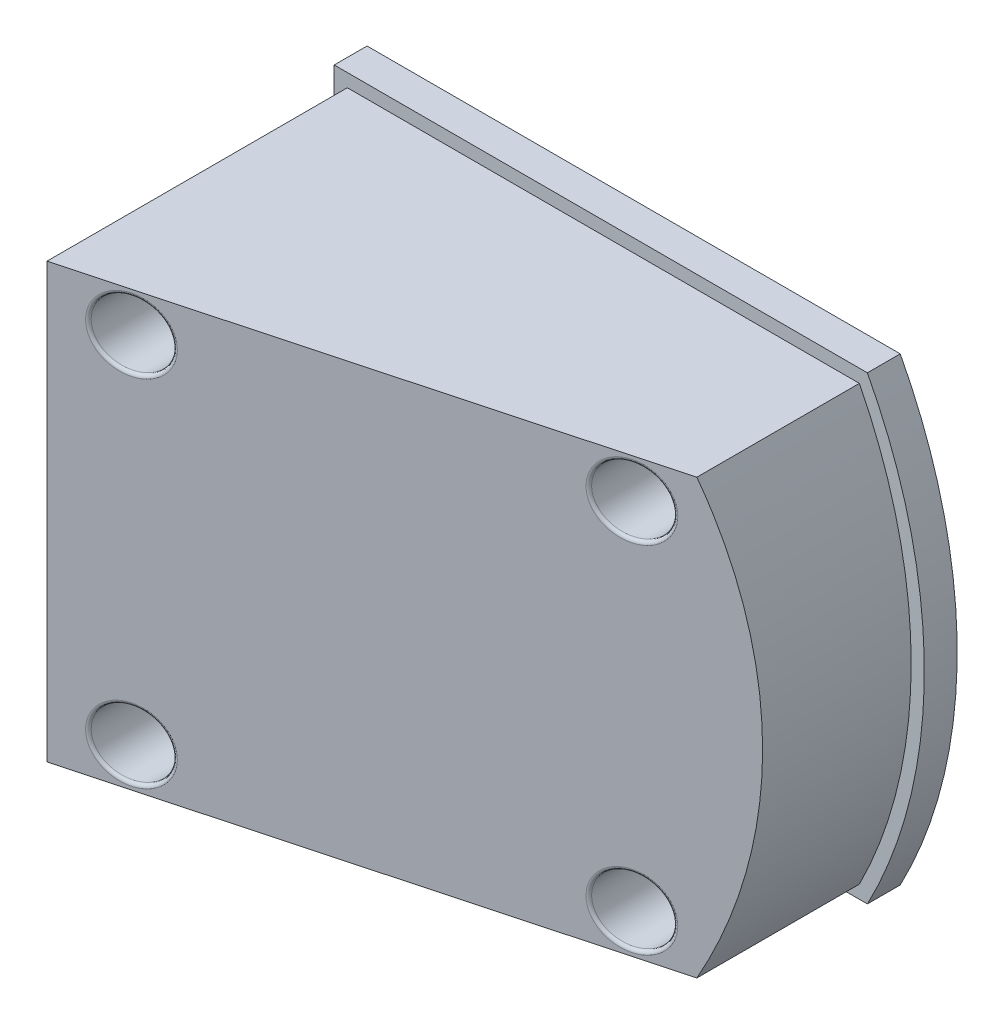
SolidWorks part; units mm, degrees
note: The reader was unsure of these and kept them because the rebuilt part matched: shared geometry of "Sketch3<2>".
material "1060 Alloy"
ref_plane "Front Plane" through (0, 0, 0) normal (0, 0, 1) x (1, 0, 0)
ref_plane "Top Plane" through (0, 0, 0) normal (0, 1, 0) x (1, 0, 0)
ref_plane "Right Plane" through (0, 0, 0) normal (1, 0, 0) x (0, 0, -1)
sketch "Sketch1" plane through (0, 0, 0) normal (0, 0, 1) x (1, 0, 0)
  line L3 (-14.8019, 35) -> (-14.8019, -35)
  line L4 (-14.8019, -35) -> (66.3325, -35)
  line L5 (66.3325, 35) -> (-14.8019, 35)
  line L6 (-14.8019, 35) -> (-14.8019, -35)
  line L7 (-14.8019, -35) -> (66.3325, -35)
  line L8 (66.3325, 35) -> (-14.8019, 35)
  arc A1 (66.3325, -35) -> (66.3325, 35) centre (0, 0) ccw
  arc A2 (66.3325, -35) -> (66.3325, 35) centre (0, 0) ccw
  dimension "D1" = 0
extrude "Boss-Extrude1" add sketch "Sketch1" along normal blind 5
sketch "Sketch2" plane through (0, 0, 5) normal (0, 0, 1) x (1, 0, 0)
  line L6 (65.1153, 33) -> (-12.8019, 33)
  line L7 (-12.8019, 33) -> (-12.8019, -33)
  line L8 (-12.8019, -33) -> (65.1153, -33)
  line L9 (65.1153, 33) -> (-12.8019, 33)
  line L10 (-12.8019, 33) -> (-12.8019, -33)
  line L11 (-12.8019, -33) -> (65.1153, -33)
  arc A2 (65.1153, -33) -> (65.1153, 33) centre (0, 0) ccw
  arc A3 (65.1153, -33) -> (65.1153, 33) centre (0, 0) ccw
  dimension "D1" = 2
extrude "Boss-Extrude2" add sketch "Sketch2" along normal up to surface (45.7085 mm away)
sketch "Sketch3" plane through (0, 0, 0) normal (0, 0, -1) x (-1, 0, 0)
  line L0 (14.8019, 35) -> (14.8019, -35) construction
  line L1 (-66.3325, 35) -> (14.8019, 35) construction
  line L2 (2.8019, 27) -> (-57.1981, 27) construction
  line L3 (0, 0) -> (-53.0063, 0) construction
  line L4 (2.8019, -27) -> (-57.1981, -27) construction
  circle A0 centre (2.8019, 27) radius 5
  circle A1 centre (-57.1981, 27) radius 5
  circle A2 centre (-57.1981, -27) radius 5
  circle A3 centre (2.8019, -27) radius 5
  dimension "D1" = 10
  dimension "D2" = 12
  dimension "D4" = 10
  dimension "D3" = 8
  dimension "D5" = 60
extrude "Cut-Extrude1" cut sketch "Sketch3" against normal through all from offset 37 offset against normal yes
extrude "Cut-Extrude2" cut sketch "Sketch3<2>" against normal through all from offset 22 contours A1 | A2 offset against normal yes
sketch "Sketch3<2>" plane through (0, 0, 0) normal (0, 0, -1) x (-1, 0, 0) same geometry as "Sketch3"
sketch "Sketch4" plane through (0, 0, 0) normal (0, 0, -1) x (-1, 0, 0)
  circle A0 centre (-57.1981, 27) radius 3
  circle A1 centre (2.8019, 27) radius 3
  circle A2 centre (2.8019, -27) radius 3
  circle A3 centre (-57.1981, -27) radius 3
  dimension "D1" = 6
extrude "Cut-Extrude3" cut sketch "Sketch4" against normal through all
fillet "Fillet1" radius 0.5 5 edges at (52.1981, 27, 22) (62.1981, 27, 30.5162) (2.1981, 27, 46.67) (62.1981, -27, 30.5162) (2.1981, -27, 46.67)
